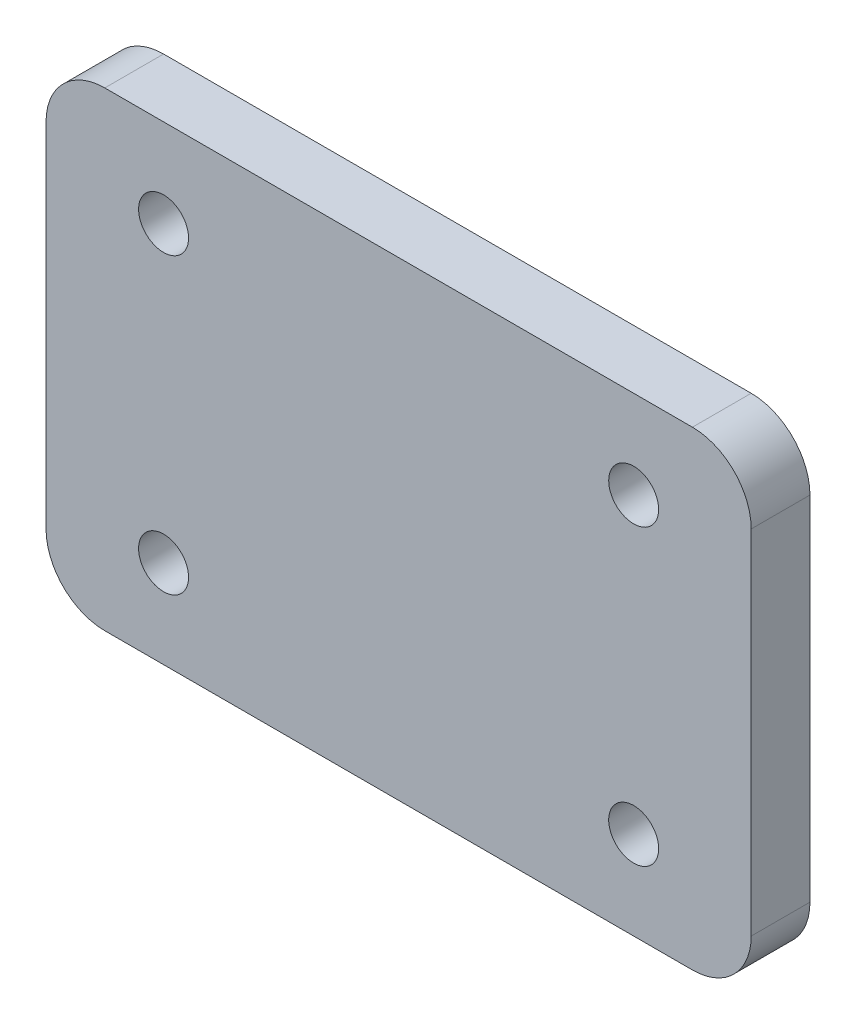
SolidWorks part; units mm, degrees
material "1.4003 (X2CrNi12)"
ref_plane "Ön Düzlem" through (0, 0, 0) normal (0, 0, 1) x (1, 0, 0)
ref_plane "Üst Düzlem" through (0, 0, 0) normal (0, 1, 0) x (1, 0, 0)
ref_plane "Sağ Düzlem" through (0, 0, 0) normal (1, 0, 0) x (0, 0, -1)
sketch "Çizim1" plane through (0, 0, 0) normal (0, 0, 1) x (1, 0, 0)
  line L1 (-60, 40) -> (60, 40)
  line L2 (-60, 40) -> (-60, -40)
  line L3 (-60, -40) -> (60, -40)
  line L4 (60, 40) -> (60, -40)
  line L5 (-60, 40) -> (60, -40) construction
  line L6 (-60, -40) -> (60, 40) construction
  point P0 (0, 0)
  dimension "D1" = 80
  dimension "D2" = 120
base flange "Taban-Flanş1" sketch "Çizim1" thickness 10 reverse thickness direction no parameters "D1"=2
sketch "Çizim6" plane through (0, 0, 0) normal (0, 0, 1) x (1, 0, 0)
  line L0 (-60, 40) -> (-60, -40) construction
  line L1 (60, 40) -> (-60, 40) construction
  line L2 (0, 0) -> (0, 40) construction
  line L3 (0, 0) -> (60, 0) construction
  line L4 (60, -40) -> (60, 40) construction
  circle A0 centre (-40, 25) radius 4.25
  circle A2 centre (40, 25) radius 4.25
  circle A3 centre (40, -25) radius 4.25
  circle A4 centre (-40, -25) radius 4.25
  dimension "D1" = 8.5
  dimension "D2" = 20
  dimension "D3" = 15
extrude "Kes-Ekstrüzyon1" cut sketch "Çizim6" against normal blind 20
cosmetic thread "Kozmetik Diş Açma2"
cosmetic thread "Kozmetik Diş Açma3"
cosmetic thread "Kozmetik Diş Açma4"
cosmetic thread "Kozmetik Diş Açma5"
fillet "Radyus1" radius 10 4 edges at (60, 40, -5) (60, -40, -5) (-60, -40, -5) (-60, 40, -5)
sketch "Büküm-Çizgileri1" [suppressed] plane through (0, 0, 0) normal (0, 1, 0) x (1, 0, 0)
sketch "Sınırlandırma-Kutusu1" [suppressed] plane through (0, 0, 0) normal (0, 1, 0) x (1, 0, 0)
sheet metal parameters "Sac-Levha1" thickness 10 parameters "D1"=2
flat pattern "Düz-Çoğaltma1" [suppressed]
sketch "Büküm-Çizgileri2" plane through (0, 0, 0) normal (0, 1, 0) x (1, 0, 0)
sketch3d "Sınırlandırma-Kutusu2" [suppressed]
  line L0 (60, -40, 0) -> (-60, -40, 0) construction
  line L1 (60, 40, 0) -> (-60, 40, 0) construction
  line L2 (60, -40, 0) -> (60, 40, 0) construction
  line L3 (-60, -40, 0) -> (-60, 40, 0) construction
sheet metal parameters "Sac-Levha2" thickness 10 parameters "D1"=2
flat pattern "Düz-Çoğaltma1"
sketch "Büküm-Çizgileri2" plane through (0, 0, 0) normal (0, 1, 0) x (1, 0, 0)
sketch3d "Sınırlandırma-Kutusu2" [suppressed]
  line L0 (-60, -40, 0) -> (60, -40, 0) construction
  line L1 (-60, 40, 0) -> (60, 40, 0) construction
  line L2 (-60, -40, 0) -> (-60, 40, 0) construction
  line L3 (60, -40, 0) -> (60, 40, 0) construction
